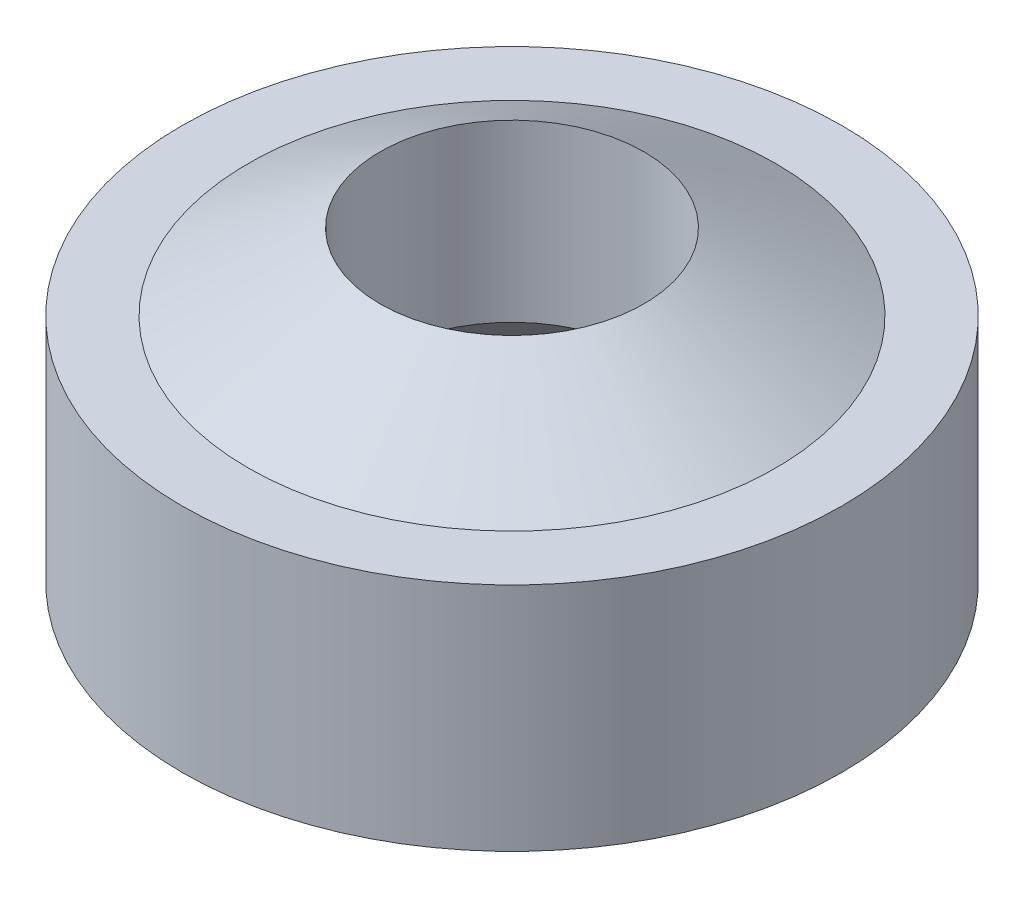
SolidWorks part; units mm, degrees
material "Silicon"
ref_plane "Front Plane" through (0, 0, 0) normal (0, 0, 1) x (1, 0, 0)
ref_plane "Top Plane" through (0, 0, 0) normal (0, 1, 0) x (1, 0, 0)
ref_plane "Right Plane" through (0, 0, 0) normal (1, 0, 0) x (0, 0, -1)
sketch "Sketch2" plane through (0, 0, 0) normal (0, 0, 1) x (1, 0, 0)
  line L0 (0, 50.6241) -> (0, -35.5329)
ref_axis "Axis1" through (0, 50.6241, 0) along (0, -1, 0)
sketch "Sketch3" plane through (0, 0, 0) normal (0, 0, 1) x (1, 0, 0)
  line L0 (0, 50.6241) -> (0, -35.5329) construction
  line L2 (7, 1) -> (7, 3)
  line L3 (8, 6) -> (10, 6)
  line L4 (10, -1) -> (10, 6)
  line L5 (4, 6) -> (4, 3)
  line L8 (7, 3) -> (4, 3)
  line L11 (4, 6) -> (4, 10)
  line L13 (7, 1) -> (7, -1)
  line L14 (7, -1) -> (10, -1)
  line L15 (8, 6) -> (8, 10)
  line L16 (8, 10) -> (4, 10)
  dimension "D1" = 7
  dimension "D2" = 2
  dimension "D3" = 4
  dimension "D4" = 3
  dimension "D5" = 4
  dimension "D6" = 0
  dimension "D7" = 4
  dimension "D8" = 7
  dimension "D9" = 11
revolve "Revolve2" add sketch "Sketch3" angle 360 about L0 region at (7.0435, 4.8043, 0)
chamfer "Chamfer6" distance 4 angle 60 1 edges at (0, 10, 8) first distance on face at (0, 10, 8)
chamfer "Chamfer4" distance 2 angle 45 1 edges at (0, -1, 7)
